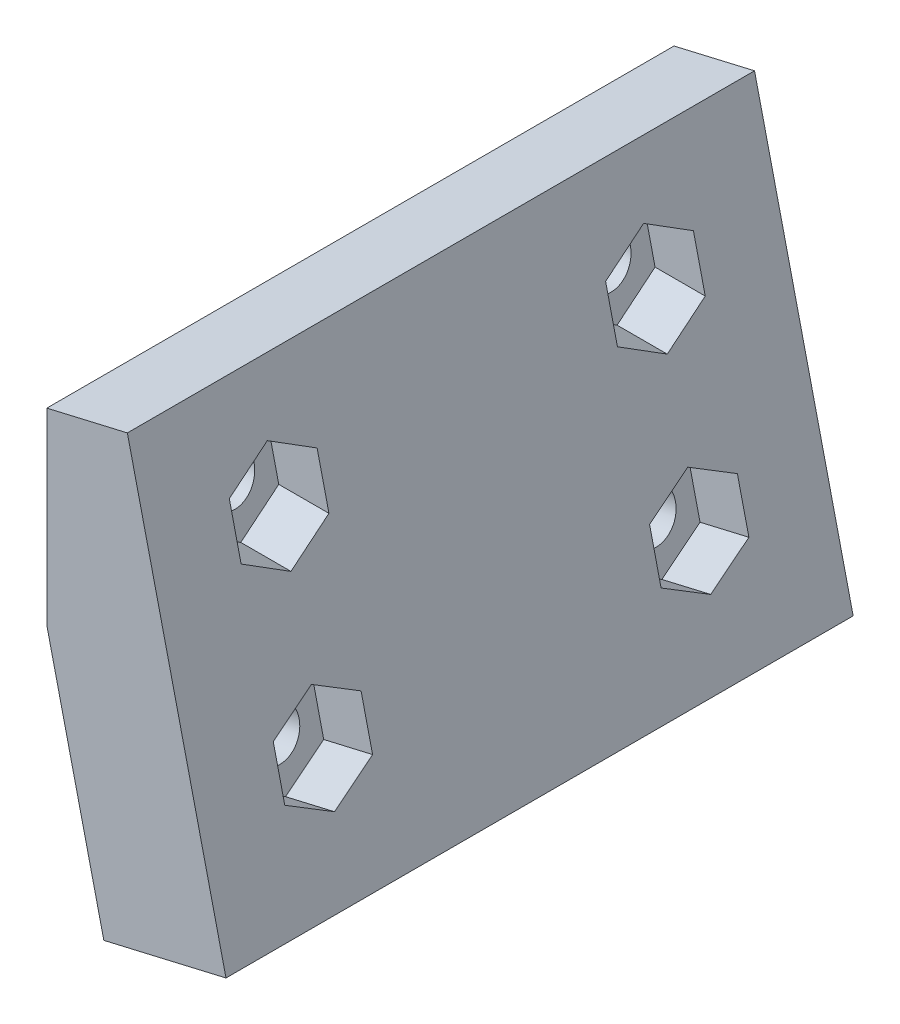
SolidWorks part; units mm, degrees
material "ABS"
ref_plane "Front Plane" through (0, 0, 0) normal (0, 0, 1) x (1, 0, 0)
ref_plane "Top Plane" through (0, 0, 0) normal (0, 1, 0) x (1, 0, 0)
ref_plane "Right Plane" through (0, 0, 0) normal (1, 0, 0) x (0, 0, -1)
sketch "Sketch1" plane through (0, 0, 0) normal (0, 0, 1) x (1, 0, 0)
  line L0 (0, -110.5) -> (0, -125.5)
  line L1 (0, -125.5) -> (0, 24.5) construction
  line L2 (0, -125.5) -> (4.5442, -144.9769)
  line L3 (0, -125.5) -> (21.7, -218.5082) construction
  line L4 (4.5442, -144.9769) -> (14.2827, -142.7048)
  line L5 (14.2827, -142.7048) -> (6.4194, -109.0023)
  line L6 (6.4194, -109.0023) -> (0, -110.5)
  dimension "D1" = 15
  dimension "D2" = 20
  dimension "D3" = 10
extrude "Boss-Extrude1" add sketch "Sketch1" against normal blind 50
sketch "Sketch2" plane through (0, 0, 0) normal (-1, 0, 0) x (0, 0, 1)
  line L0 (-50, -118) -> (0, -118) construction
  line L1 (-50, -110.5) -> (0, -110.5)
  line L2 (-50, -110.5) -> (-50, -125.5)
  line L3 (-50, -125.5) -> (0, -125.5)
  line L4 (0, -110.5) -> (0, -125.5)
  line L5 (-50, -110.5) -> (0, -125.5) construction
  line L6 (-50, -125.5) -> (0, -110.5) construction
  line L7 (-25, -110.5) -> (-25, -125.5) construction
  line L8 (-40, -113.9585) -> (-43.5, -115.9793)
  line L9 (-43.5, -115.9793) -> (-43.5, -120.0207)
  line L10 (-43.5, -120.0207) -> (-40, -122.0415)
  line L11 (-40, -122.0415) -> (-36.5, -120.0207)
  line L12 (-36.5, -120.0207) -> (-36.5, -115.9793)
  line L13 (-36.5, -115.9793) -> (-40, -113.9585)
  line L20 (-13.5, -115.9793) -> (-10, -113.9585)
  line L21 (-13.5, -120.0207) -> (-13.5, -115.9793)
  line L22 (-10, -122.0415) -> (-13.5, -120.0207)
  line L23 (-6.5, -120.0207) -> (-10, -122.0415)
  line L24 (-6.5, -115.9793) -> (-6.5, -120.0207)
  line L25 (-10, -113.9585) -> (-6.5, -115.9793)
  circle A0 centre (-40, -118) radius 3.5 construction
  circle A1 centre (-40, -118) radius 2
  circle A2 centre (-10, -118) radius 3.5 construction
  circle A3 centre (-10, -118) radius 2
  point P4 (-25, -118)
  dimension "D1" = 4
  dimension "D2" = 7
  dimension "D3" = 15
extrude "Cut-Extrude1" cut sketch "Sketch2" against normal blind 50 contours A1 | A3 region at (0, -118, -40) region at (0, -118, -10)
extrude "Cut-Extrude2" cut sketch "Sketch2<3>" along normal blind 4 from surface contours L12 L13 L8 L9 L10 L11 A1 | L25 L20 L21 L22 L23 L24 A3 region at (0, -115.0615, -38.3035) region at (0, -115.0615, -11.6965) starting at face at (8.0521, -116, -10)
sketch "Sketch2<3>" plane through (0, 0, 0) normal (-1, 0, 0) x (0, 0, 1) same geometry as "Sketch2"
sketch "Sketch3" plane through (-27.7691, -6.4789, 0) normal (-0.9738, -0.2272, 0) x (0, 0, 1)
  line L0 (0, -132.2176) -> (-50, -132.2176) construction
  line L1 (-50, -122.2176) -> (0, -122.2176)
  line L2 (-50, -122.2176) -> (-50, -142.2176)
  line L3 (-50, -142.2176) -> (0, -142.2176)
  line L4 (0, -122.2176) -> (0, -142.2176)
  line L5 (-50, -122.2176) -> (0, -142.2176) construction
  line L6 (-50, -142.2176) -> (0, -122.2176) construction
  line L7 (-25, -122.2176) -> (-25, -142.2176) construction
  line L8 (-40, -128.1762) -> (-43.5, -130.1969)
  line L9 (-43.5, -130.1969) -> (-43.5, -134.2384)
  line L10 (-43.5, -134.2384) -> (-40, -136.2591)
  line L11 (-40, -136.2591) -> (-36.5, -134.2384)
  line L12 (-36.5, -134.2384) -> (-36.5, -130.1969)
  line L13 (-36.5, -130.1969) -> (-40, -128.1762)
  line L14 (-13.5, -130.1969) -> (-10, -128.1762)
  line L15 (-13.5, -134.2384) -> (-13.5, -130.1969)
  line L16 (-10, -136.2591) -> (-13.5, -134.2384)
  line L17 (-6.5, -134.2384) -> (-10, -136.2591)
  line L18 (-6.5, -130.1969) -> (-6.5, -134.2384)
  line L19 (-10, -128.1762) -> (-6.5, -130.1969)
  circle A0 centre (-40, -132.2176) radius 2
  circle A1 centre (-40, -132.2176) radius 3.5 construction
  circle A2 centre (-10, -132.2176) radius 3.5 construction
  circle A3 centre (-10, -132.2176) radius 2
  point P4 (-25, -132.2176)
  dimension "D1" = 10
  dimension "D3" = 4
  dimension "D2" = 7
extrude "Cut-Extrude3" cut sketch "Sketch3" against normal through all contours A0 | A3 region at (2.2721, -135.2385, -40) region at (2.2721, -135.2385, -10)
extrude "Cut-Extrude4" cut sketch "Sketch3<3>" along normal blind 4 from surface contours L12 L13 L8 L9 L10 L11 A0 | L19 L14 L15 L16 L17 L18 A3 region at (1.6044, -132.3768, -38.3035) region at (1.6044, -132.3768, -11.6965) starting at face at (11.5561, -131.0187, -10)
sketch "Sketch3<3>" plane through (-27.7691, -6.4789, 0) normal (-0.9738, -0.2272, 0) x (0, 0, 1) same geometry as "Sketch3"
